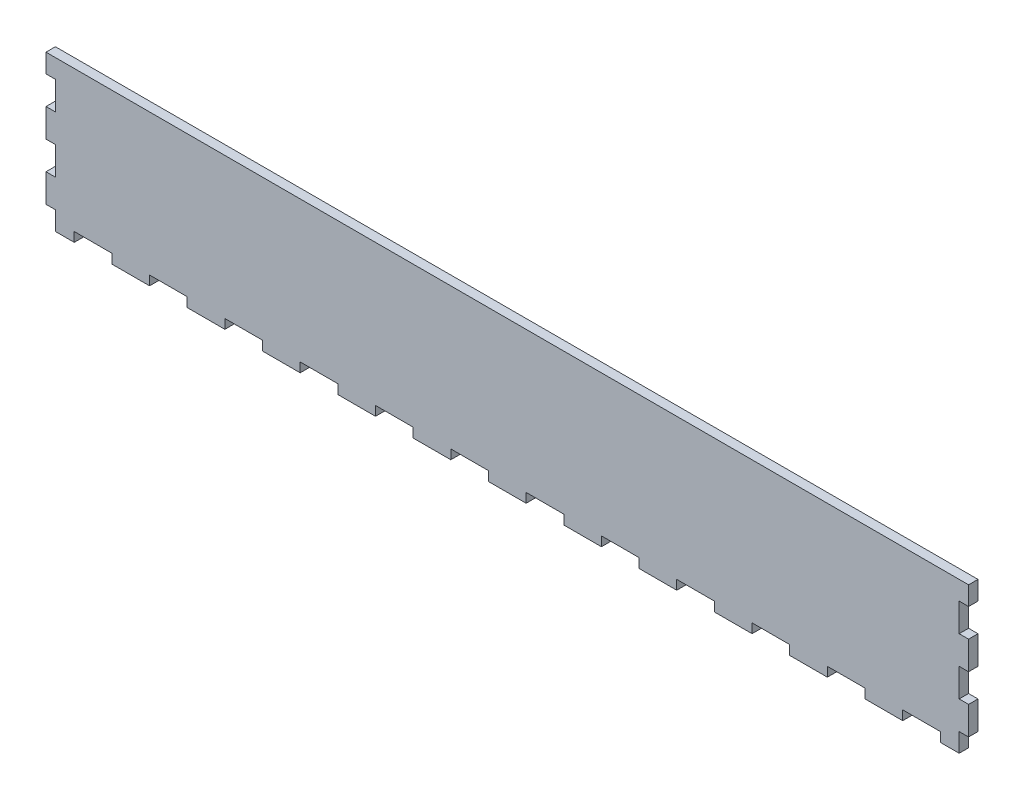
SolidWorks part; units mm, degrees
material "Oak"
ref_plane "Front Plane" through (0, 0, 0) normal (0, 0, 1) x (1, 0, 0)
ref_plane "Top Plane" through (0, 0, 0) normal (0, 1, 0) x (1, 0, 0)
ref_plane "Right Plane" through (0, 0, 0) normal (1, 0, 0) x (0, 0, -1)
sketch "Sketch2" plane through (0, 0, 0) normal (0, 0, 1) x (1, 0, 0)
  line L0 (-311.15, 38.1) -> (-304.8, 38.1)
  line L1 (-304.8, -50.8) -> (-292.1, -50.8)
  line L2 (-311.15, -38.1) -> (-311.15, -19.05)
  line L3 (-311.15, 50.8) -> (311.15, 50.8)
  line L5 (-311.15, -50.8) -> (311.15, 50.8) construction
  line L6 (-311.15, 50.8) -> (311.15, -50.8) construction
  line L7 (-304.8, 38.1) -> (-304.8, 19.05)
  line L8 (-304.8, 19.05) -> (-311.15, 19.05)
  line L9 (-311.15, 38.1) -> (-311.15, 50.8)
  line L10 (-311.15, 0) -> (-304.8, 0)
  line L11 (-304.8, 0) -> (-304.8, -19.05)
  line L12 (-304.8, -19.05) -> (-311.15, -19.05)
  line L13 (-311.15, -38.1) -> (-304.8, -38.1)
  line L14 (-304.8, -38.1) -> (-304.8, -50.8)
  line L15 (-311.15, 0) -> (-311.15, 19.05)
  line L16 (0, -55.88) -> (0, 55.88) construction
  line L17 (311.15, 0) -> (311.15, 19.05)
  line L18 (304.8, -38.1) -> (304.8, -50.8)
  line L19 (311.15, -38.1) -> (304.8, -38.1)
  line L20 (304.8, -19.05) -> (311.15, -19.05)
  line L21 (304.8, 0) -> (304.8, -19.05)
  line L22 (311.15, 0) -> (304.8, 0)
  line L23 (311.15, 38.1) -> (311.15, 50.8)
  line L24 (304.8, 19.05) -> (311.15, 19.05)
  line L25 (304.8, 38.1) -> (304.8, 19.05)
  line L26 (311.15, -38.1) -> (311.15, -19.05)
  line L27 (311.15, 38.1) -> (304.8, 38.1)
  line L28 (-292.1, -50.8) -> (-292.1, -44.45)
  line L29 (-292.1, -44.45) -> (-266.7, -44.45)
  line L30 (-266.7, -44.45) -> (-266.7, -50.8)
  line L31 (-266.7, -50.8) -> (-241.3, -50.8)
  line L32 (-241.3, -50.8) -> (-241.3, -44.45)
  line L33 (-241.3, -44.45) -> (-215.9, -44.45)
  line L34 (-215.9, -44.45) -> (-215.9, -50.8)
  line L35 (-190.5, -50.8) -> (-190.5, -44.45)
  line L36 (-190.5, -44.45) -> (-165.1, -44.45)
  line L37 (-165.1, -44.45) -> (-165.1, -50.8)
  line L38 (-139.7, -50.8) -> (-139.7, -44.45)
  line L39 (-139.7, -44.45) -> (-114.3, -44.45)
  line L40 (-114.3, -44.45) -> (-114.3, -50.8)
  line L41 (-88.9, -50.8) -> (-88.9, -44.45)
  line L42 (-88.9, -44.45) -> (-63.5, -44.45)
  line L43 (-63.5, -44.45) -> (-63.5, -50.8)
  line L44 (-38.1, -50.8) -> (-38.1, -44.45)
  line L45 (-38.1, -44.45) -> (-12.7, -44.45)
  line L46 (-12.7, -44.45) -> (-12.7, -50.8)
  line L47 (12.7, -50.8) -> (12.7, -44.45)
  line L48 (12.7, -44.45) -> (38.1, -44.45)
  line L49 (38.1, -44.45) -> (38.1, -50.8)
  line L50 (63.5, -50.8) -> (63.5, -44.45)
  line L51 (63.5, -44.45) -> (88.9, -44.45)
  line L52 (88.9, -44.45) -> (88.9, -50.8)
  line L53 (114.3, -50.8) -> (114.3, -44.45)
  line L54 (114.3, -44.45) -> (139.7, -44.45)
  line L55 (139.7, -44.45) -> (139.7, -50.8)
  line L56 (165.1, -50.8) -> (165.1, -44.45)
  line L57 (165.1, -44.45) -> (190.5, -44.45)
  line L58 (190.5, -44.45) -> (190.5, -50.8)
  line L59 (215.9, -50.8) -> (215.9, -44.45)
  line L60 (215.9, -44.45) -> (241.3, -44.45)
  line L61 (241.3, -44.45) -> (241.3, -50.8)
  line L62 (266.7, -50.8) -> (266.7, -44.45)
  line L63 (266.7, -44.45) -> (292.1, -44.45)
  line L64 (292.1, -44.45) -> (292.1, -50.8)
  line L65 (-215.9, -50.8) -> (-190.5, -50.8)
  line L66 (-165.1, -50.8) -> (-139.7, -50.8)
  line L67 (-114.3, -50.8) -> (-88.9, -50.8)
  line L68 (-63.5, -50.8) -> (-38.1, -50.8)
  line L69 (-12.7, -50.8) -> (12.7, -50.8)
  line L70 (38.1, -50.8) -> (63.5, -50.8)
  line L71 (88.9, -50.8) -> (114.3, -50.8)
  line L72 (139.7, -50.8) -> (165.1, -50.8)
  line L73 (190.5, -50.8) -> (215.9, -50.8)
  line L74 (241.3, -50.8) -> (266.7, -50.8)
  line L75 (292.1, -50.8) -> (304.8, -50.8)
  point P0 (0, 0)
  dimension "D1" = 12.7
  dimension "D2" = 101.6
  dimension "D3" = 6.35
  dimension "D4" = 19.05
  dimension "D5" = 19.05
  dimension "D6" = 19.05
  dimension "D7" = 19.05
  dimension "D8" = 25.4
  dimension "D9" = 622.3
  dimension "D10" = 6.35
  dimension "D11" = 12.7
  dimension "D13" = 25.4
  dimension "D12" = 12
extrude "Boss-Extrude1" add sketch "Sketch2" along normal blind 6.35
sketch "Sketch3" plane through (0, 0, 0) normal (0, 0, -1) x (-1, 0, 0)
  line L0 (-126.5375, 3.6108) -> (255.6426, 3.6108) construction
  text T0 "EECS 106A FINAL PROJECT | TRAY\r\nAllen, Josh, Leo, Rajiv, MPC Lab" font "Century Gothic" height 12.7
  point P3 (0, 0)
  point P4 (255.6426, -17.6687)
  point P5 (-126.5375, -18.9455)
extrude "Cut-Extrude1" cut sketch "Sketch3" against normal blind 1.27
